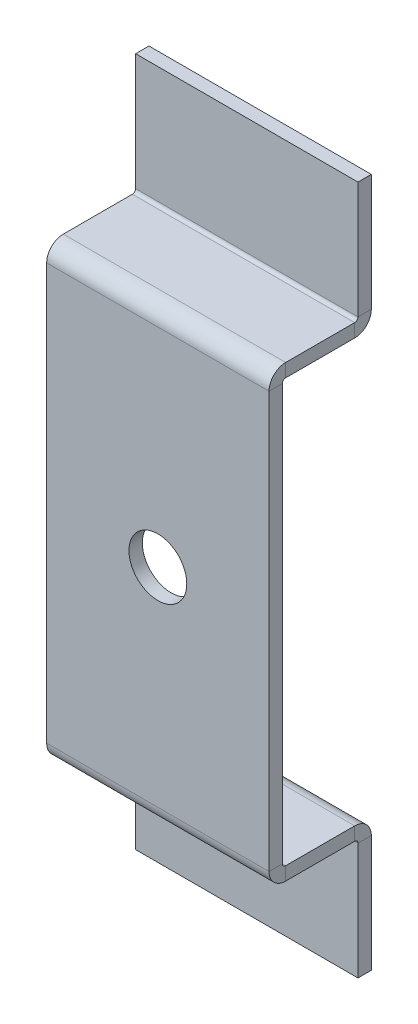
SolidWorks part; units mm, degrees
note: The reader was unsure of these and kept them because the rebuilt part matched: flange length of "边线-法兰1", "边线-法兰2".
ref_plane "前视基准面" through (0, 0, 0) normal (0, 0, 1) x (1, 0, 0)
ref_plane "上视基准面" through (0, 0, 0) normal (0, 1, 0) x (1, 0, 0)
ref_plane "右视基准面" through (0, 0, 0) normal (1, 0, 0) x (0, 0, -1)
other "Configuration Table"
sketch "草图1" plane through (0, 0, 0) normal (0, 0, 1) x (1, 0, 0)
  line L1 (0, 0) -> (50, 0)
  line L2 (0, 0) -> (0, 95)
  line L3 (0, 95) -> (50, 95)
  line L4 (50, 0) -> (50, 95)
  dimension "D1" = 95
  dimension "D2" = 50
base flange "基体-法兰1" sketch "草图1" thickness 3 reverse thickness direction no parameters "D1"=0.7366
edge flange "边线-法兰1" sketch "草图10" flange profiles "草图10", "草图11" flange angle 90 flange length 20 flange position material outside bend radius 0.7366 thickness 3 relief rectangular parameters "D6"=10, "D8"=1
sketch "草图10" plane through (0, 95, -3) normal (0, -1, 0) x (-1, 0, 0)
  line L2 (-50, 0) -> (-50, 17)
  line L3 (-50, 17) -> (0, 17)
  line L4 (0, 17) -> (0, 0)
  line L5 (0, 0) -> (-50, 0) construction
  line L6 (0, 0) -> (-50, 0)
sketch "草图11" plane through (0, 0, -3) normal (0, 1, 0) x (1, 0, 0)
  line L0 (50, 0) -> (0, 0) construction
  line L1 (50, 0) -> (0, 0)
  line L2 (50, 0) -> (50, 17)
  line L3 (50, 17) -> (0, 17)
  line L4 (0, 17) -> (0, 0)
bend "边线折弯1" bend radius 0.7366 bend angle 90 parameters "D5"=1
bend "边线折弯2" bend radius 0.7366 bend angle 90 parameters "D5"=2
edge flange "边线-法兰2" sketch "草图16" flange profiles "草图16", "草图17" flange angle 90 flange length 30 flange position material outside bend radius 0.7366 thickness 3 relief rectangular parameters "D6"=10, "D8"=1
sketch "草图16" plane through (0, -3, -20) normal (0, 0, -1) x (1, 0, 0)
  line L2 (0, 0) -> (0, 27)
  line L3 (0, 27) -> (50, 27)
  line L4 (50, 27) -> (50, 0)
  line L7 (50, 0) -> (0, 0) construction
  line L8 (50, 0) -> (0, 0)
sketch "草图17" plane through (0, 98, -20) normal (0, 0, -1) x (-1, 0, 0)
  line L0 (0, 0) -> (-50, 0) construction
  line L1 (0, 0) -> (-50, 0)
  line L2 (-50, 0) -> (-50, 27)
  line L3 (-50, 27) -> (0, 27)
  line L4 (0, 27) -> (0, 0)
bend "边线折弯3" bend radius 0.7366 bend angle 90 parameters "D5"=3
bend "边线折弯4" bend radius 0.7366 bend angle 90 parameters "D5"=4
sketch "草图18" plane through (0, 0, 0) normal (0, 0, 1) x (1, 0, 0)
  line L7 (50, -30) -> (0, -30) construction
  line L8 (50, 0.7366) -> (50, 94.2634) construction
  circle A0 centre (25, 47.5) radius 6.5
  dimension "D5" = 13
  dimension "D3" = 77.5
  dimension "D4" = 25
extrude "切除-拉伸1" cut sketch "草图18" against normal through all normal cut yes
sketch "折弯-线1" plane through (0, 0, 0) normal (0, 1, 0) x (1, 0, 0)
sketch "边界框1" plane through (0, 0, 0) normal (0, 1, 0) x (1, 0, 0)
sheet metal parameters "钣金6" thickness 3 parameters "D1"=0.7366
flat pattern "平板型式6" [suppressed]
sketch "折弯-线2" plane through (0, 0, 0) normal (0, 1, 0) x (1, 0, 0)
sketch "边界框2" [suppressed] plane through (0, 0, 0) normal (0, 1, 0) x (1, 0, 0)
sheet metal parameters "钣金7" thickness 3 parameters "D1"=0.7366
flat pattern "平板型式6" [suppressed]
sketch "折弯-线2" plane through (0, 0, 0) normal (0, 1, 0) x (1, 0, 0)
sketch "边界框2" [suppressed] plane through (0, 0, 0) normal (0, 1, 0) x (1, 0, 0)
bend of the flat pattern "展平-<边线折弯1>1"
bend of the flat pattern "展平-<边线折弯2>1"
sheet metal parameters "钣金8" thickness 3 parameters "D1"=0.7366
flat pattern "平板型式6" [suppressed]
sketch "折弯-线2" plane through (0, 0, 0) normal (0, 1, 0) x (1, 0, 0)
sketch "边界框2" [suppressed] plane through (0, 0, 0) normal (0, 1, 0) x (1, 0, 0)
bend of the flat pattern "展平-<边线折弯1>1"
bend of the flat pattern "展平-<边线折弯2>1"
bend of the flat pattern "展平-<边线折弯3>1"
bend of the flat pattern "展平-<边线折弯4>1"
sheet metal parameters "钣金9" thickness 3 parameters "D1"=0.7366
flat pattern "平板型式6" [suppressed]
sketch "折弯-线2" plane through (0, 0, 0) normal (0, 1, 0) x (1, 0, 0)
sketch "边界框2" [suppressed] plane through (0, 0, 0) normal (0, 1, 0) x (1, 0, 0)
bend of the flat pattern "展平-<边线折弯1>1"
bend of the flat pattern "展平-<边线折弯2>1"
bend of the flat pattern "展平-<边线折弯3>1"
bend of the flat pattern "展平-<边线折弯4>1"
